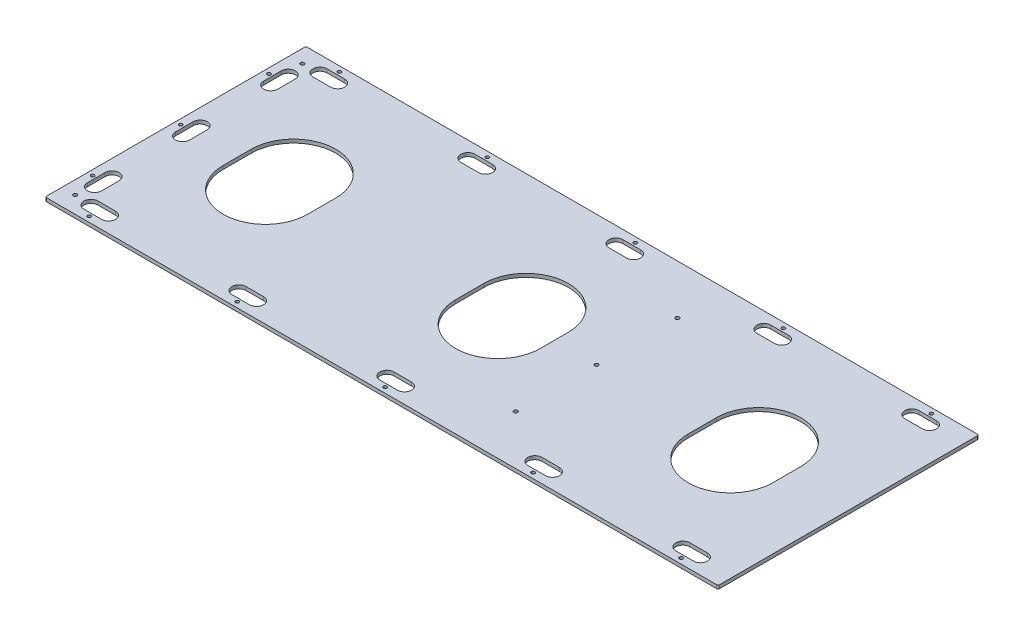
SolidWorks part; units mm, degrees
material "PC High Viscosity"
ref_plane "Front Plane" through (0, 0, 0) normal (0, 0, 1) x (1, 0, 0)
ref_plane "Top Plane" through (0, 0, 0) normal (0, 1, 0) x (1, 0, 0)
ref_plane "Right Plane" through (0, 0, 0) normal (1, 0, 0) x (0, 0, -1)
sketch "Sketch1" plane through (0, 0, 0) normal (0, 1, 0) x (1, 0, 0)
  line L0 (0, 0) -> (0, 469.9)
  line L1 (0, 469.9) -> (1212.85, 469.9)
  line L5 (1212.85, 0) -> (0, 0)
  line L6 (1212.85, 0) -> (1212.85, 469.9)
  dimension "D1" = 469.9
  dimension "D3" = 1212.85
extrude "Boss-Extrude1" add sketch "Sketch1" along normal blind 6.35
sketch "Sketch2" plane through (0, 6.35, 0) normal (0, 1, 0) x (1, 0, 0)
  line L0 (0, 234.95) -> (1212.85, 234.95) construction
  line L1 (0, 469.9) -> (0, 0) construction
  line L2 (1212.85, 0) -> (1212.85, 469.9) construction
  line L3 (187.325, 260.35) -> (187.325, 209.55) construction
  line L4 (263.525, 260.35) -> (263.525, 209.55)
  line L5 (111.125, 260.35) -> (111.125, 209.55)
  line L6 (606.425, 260.35) -> (606.425, 209.55) construction
  line L7 (682.625, 260.35) -> (682.625, 209.55)
  line L8 (530.225, 260.35) -> (530.225, 209.55)
  line L9 (1025.525, 260.35) -> (1025.525, 209.55) construction
  line L10 (1101.725, 260.35) -> (1101.725, 209.55)
  line L11 (949.325, 260.35) -> (949.325, 209.55)
  arc A3 (263.525, 260.35) -> (111.125, 260.35) centre (187.325, 260.35) ccw
  arc A4 (111.125, 209.55) -> (263.525, 209.55) centre (187.325, 209.55) ccw
  arc A5 (682.625, 260.35) -> (530.225, 260.35) centre (606.425, 260.35) ccw
  arc A6 (530.225, 209.55) -> (682.625, 209.55) centre (606.425, 209.55) ccw
  arc A7 (1101.725, 260.35) -> (949.325, 260.35) centre (1025.525, 260.35) ccw
  arc A8 (949.325, 209.55) -> (1101.725, 209.55) centre (1025.525, 209.55) ccw
  point P2 (187.325, 234.95)
  point P14 (606.425, 234.95)
  point P21 (1025.525, 234.95)
  dimension "D4" = 50.8
  dimension "D3" = 76.2
  dimension "D1" = 419.1
  dimension "D2" = 419.1
extrude "Cut-Extrude1" cut sketch "Sketch2" against normal through all
sketch "Sketch4" plane through (0, 6.35, 0) normal (0, 1, 0) x (1, 0, 0)
  line L0 (9.525, 469.9) -> (9.525, 393.7) construction
  line L1 (1212.85, 469.9) -> (0, 469.9) construction
  line L2 (9.525, 393.7) -> (9.525, 234.95) construction
  line L3 (9.525, 234.95) -> (9.525, 76.2) construction
  line L4 (9.525, 76.2) -> (9.525, 0) construction
  line L5 (0, 0) -> (1212.85, 0) construction
  line L6 (0, 469.9) -> (0, 0) construction
  line L7 (0, 460.375) -> (69.85, 460.375) construction
  line L8 (0, 9.525) -> (69.85, 9.525) construction
  line L9 (53.975, 441.325) -> (85.725, 441.325) construction
  line L12 (28.575, 250.825) -> (28.575, 219.075) construction
  line L13 (41.275, 250.825) -> (41.275, 219.075)
  line L14 (15.875, 250.825) -> (15.875, 219.075)
  line L15 (53.975, 454.025) -> (85.725, 454.025)
  line L18 (53.975, 428.625) -> (85.725, 428.625)
  line L19 (53.975, 28.575) -> (85.725, 28.575) construction
  line L20 (53.975, 41.275) -> (85.725, 41.275)
  line L21 (53.975, 15.875) -> (85.725, 15.875)
  line L22 (28.575, 60.325) -> (28.575, 92.075) construction
  line L23 (15.875, 60.325) -> (15.875, 92.075)
  line L24 (41.275, 60.325) -> (41.275, 92.075)
  line L25 (28.575, 377.825) -> (28.575, 409.575) construction
  line L26 (15.875, 377.825) -> (15.875, 409.575)
  line L27 (41.275, 377.825) -> (41.275, 409.575)
  circle A0 centre (9.525, 393.7) radius 3.175
  circle A1 centre (9.525, 234.95) radius 3.175
  circle A2 centre (9.525, 76.2) radius 3.175
  circle A3 centre (69.85, 460.375) radius 3.175
  circle A4 centre (69.85, 9.525) radius 3.175
  arc A7 (41.275, 250.825) -> (15.875, 250.825) centre (28.575, 250.825) ccw
  arc A8 (15.875, 219.075) -> (41.275, 219.075) centre (28.575, 219.075) ccw
  arc A11 (53.975, 454.025) -> (53.975, 428.625) centre (53.975, 441.325) ccw
  arc A12 (85.725, 428.625) -> (85.725, 454.025) centre (85.725, 441.325) ccw
  arc A13 (53.975, 41.275) -> (53.975, 15.875) centre (53.975, 28.575) ccw
  arc A14 (85.725, 15.875) -> (85.725, 41.275) centre (85.725, 28.575) ccw
  arc A15 (15.875, 60.325) -> (41.275, 60.325) centre (28.575, 60.325) ccw
  arc A16 (41.275, 92.075) -> (15.875, 92.075) centre (28.575, 92.075) ccw
  arc A17 (15.875, 377.825) -> (41.275, 377.825) centre (28.575, 377.825) ccw
  arc A18 (41.275, 409.575) -> (15.875, 409.575) centre (28.575, 409.575) ccw
  point P22 (69.85, 441.325)
  point P28 (28.575, 234.95)
  point P35 (69.85, 28.575)
  point P42 (28.575, 76.2)
  point P49 (28.575, 393.7)
  dimension "D3" = 6.35
  dimension "D9" = 12.7
  dimension "D1" = 9.525
  dimension "D2" = 76.2
  dimension "D4" = 69.85
  dimension "D5" = 9.525
  dimension "D6" = 9.525
  dimension "D8" = 19.05
  dimension "D10" = 31.75
  dimension "D11" = 19.05
  dimension "D12" = 19.05
extrude "Cut-Extrude3" cut sketch "Sketch4" against normal through all
pattern_linear "LPattern1" count 5 spacing 266.7 along (1, 0, 0) of face at (69.85, 0, -457.2) of face at (69.85, 0, -6.35) of face at (69.85, 3.175, -41.275) of face at (92.075, 3.175, -28.575) of face at (47.625, 3.175, -28.575) of face at (69.85, 3.175, -15.875) of face at (47.625, 3.175, -441.325) of face at (69.85, 3.175, -454.025) of face at (92.075, 3.175, -441.325) of face at (69.85, 3.175, -428.625)
fillet "Fillet1" radius 2.54 4 edges at (1212.85, 3.175, 0) (1212.85, 3.175, -469.9) (0, 3.175, 0) (0, 3.175, -469.9)
sketch "Sketch5" plane through (0, 6.35, 0) normal (0, 1, 0) x (1, 0, 0)
  line L0 (758.825, 380.746) -> (758.825, 469.9) construction
  line L1 (1210.31, 469.9) -> (2.54, 469.9) construction
  line L2 (758.825, 380.746) -> (758.825, 234.95) construction
  line L3 (758.825, 234.95) -> (758.825, 89.154) construction
  line L4 (758.825, 89.154) -> (758.825, 0) construction
  line L5 (2.54, 0) -> (1210.31, 0) construction
  line L6 (0, 467.36) -> (0, 2.54) construction
  line L7 (1212.85, 2.54) -> (1212.85, 467.36) construction
  circle A0 centre (23.8125, 439.7375) radius 3.3782
  circle A1 centre (23.8125, 30.1625) radius 3.3782
  circle A2 centre (758.825, 89.154) radius 3.3782
  circle A3 centre (758.825, 234.95) radius 3.3782
  circle A4 centre (758.825, 380.746) radius 3.3782
  point P2 (0, 0)
  dimension "D1" = 6.7564
  dimension "D3" = 89.154
  dimension "17.875" = 454.025
  dimension "D4" = 30.1625
  dimension "D6" = 30.1625
  dimension "D7" = 23.8125
extrude "Cut-Extrude4" cut sketch "Sketch5" against normal up to surface (6.35 mm away) up to face at (1136.65, 0, -457.2)
equation "\"D6@Sketch4\"=\"D1@Sketch4\""
equation "\"D5@Sketch4\"=\"D1@Sketch4\""
equation "\"D4@Sketch4\"=2.75"
